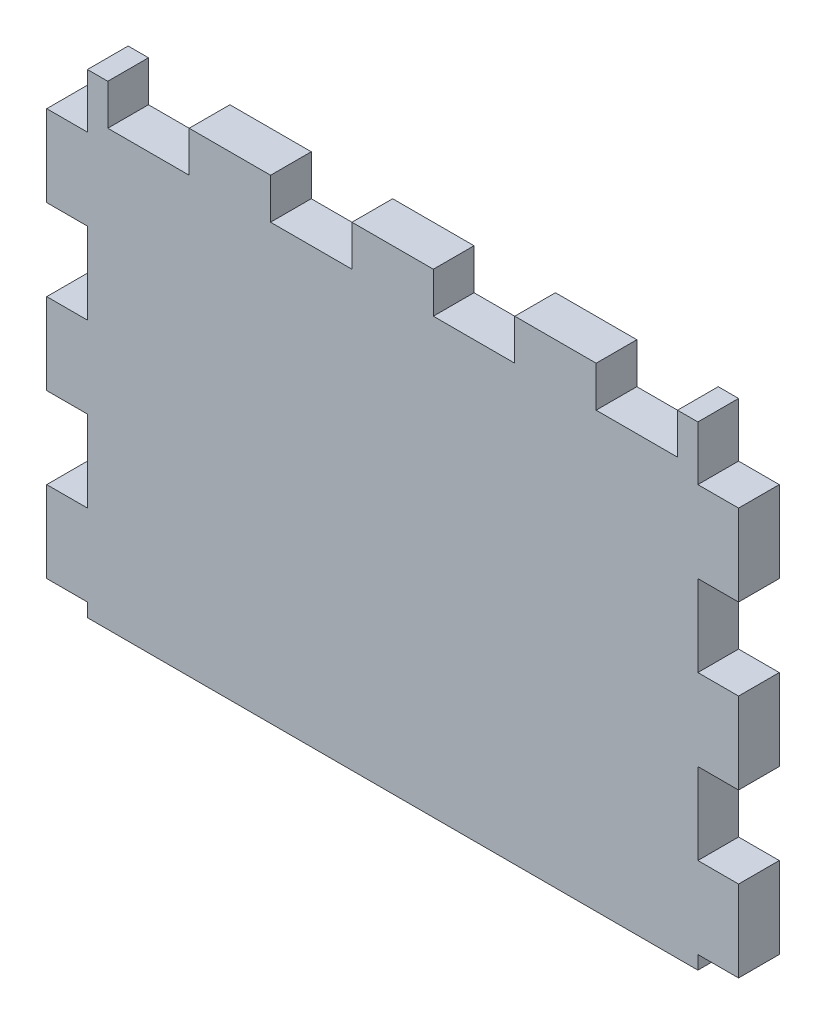
SolidWorks part; units mm, degrees
ref_plane "Front Plane" through (0, 0, 0) normal (0, 0, 1) x (1, 0, 0)
ref_plane "Top Plane" through (0, 0, 0) normal (0, 1, 0) x (1, 0, 0)
ref_plane "Right Plane" through (0, 0, 0) normal (1, 0, 0) x (0, 0, -1)
sketch "Sketch1" plane through (0, 0, 0) normal (0, 0, 1) x (1, 0, 0)
  line L1 (-22.5, 16) -> (22.5, 16)
  line L2 (-22.5, 16) -> (-22.5, -16)
  line L3 (-22.5, -16) -> (22.5, -16)
  line L4 (22.5, 16) -> (22.5, -16)
  line L5 (-22.5, 16) -> (22.5, -16) construction
  line L6 (-22.5, -16) -> (22.5, 16) construction
  point P0 (0, 0)
  dimension "D1" = 32
  dimension "D2" = 45
extrude "Boss-Extrude1" add sketch "Sketch1" along normal blind 3
sketch "Sketch2" plane through (-22.5, 0, 0) normal (-1, 0, 0) x (0, 0, 1)
  line L0 (0, 0) -> (3, 0) construction
  line L1 (0, 16) -> (0, -16) construction
  line L2 (3, 16) -> (3, -16) construction
  line L4 (3, 3) -> (0, 3)
  line L5 (3, 3) -> (3, -3)
  line L6 (3, -3) -> (0, -3)
  line L7 (0, 3) -> (0, -3)
  line L8 (3, 3) -> (0, -3) construction
  line L9 (3, -3) -> (0, 3) construction
  point P6 (1.5, 0)
  dimension "D1" = 6
extrude "Boss-Extrude2" add sketch "Sketch2" along normal blind 3
pattern_linear "LPattern1" count 2 spacing 12 along (0, -1, 0) count 2 spacing 12 along (0, 1, 0) of "Boss-Extrude2" pattern seed only yes
sketch "Sketch3" plane through (0, 16, 0) normal (0, 1, 0) x (1, 0, 0)
  line L0 (0, 0) -> (0, -3) construction
  line L1 (22.5, 0) -> (-22.5, 0) construction
  line L2 (22.5, -3) -> (-22.5, -3) construction
  line L4 (-3, 0) -> (3, 0)
  line L5 (-3, 0) -> (-3, -3)
  line L6 (-3, -3) -> (3, -3)
  line L7 (3, 0) -> (3, -3)
  line L8 (-3, 0) -> (3, -3) construction
  line L9 (-3, -3) -> (3, 0) construction
  point P6 (0, -1.5)
  dimension "D1" = 6
extrude "Boss-Extrude3" add sketch "Sketch3" along normal blind 3
pattern_linear "LPattern2" count 3 spacing 12 along (-1, 0, 0) count 3 spacing 12 along (1, 0, 0) of "Boss-Extrude3" pattern seed only yes
ref_plane "Plane1" through (0, 0, 0) normal (1, 0, 0) x (0, 0, -1)
sketch "Sketch5" plane through (0, 0, 0) normal (0, 0, -1) x (-1, 0, 0)
  line L0 (21, 19) -> (27, 19) construction
  line L1 (27, 16) -> (22.5, 16)
  line L2 (27, 16) -> (27, 19)
  line L3 (27, 19) -> (22.5, 19)
  line L4 (22.5, 16) -> (22.5, 19)
  line L5 (27, 16) -> (22.5, 19) construction
  line L6 (27, 19) -> (22.5, 16) construction
  line L8 (22.5, 16) -> (22.5, 15) construction
  point P4 (24.75, 17.5)
extrude "Cut-Extrude1" cut sketch "Sketch5" against normal blind 3
mirror "Mirror1" about plane through (0, 0, 0) normal (1, 0, 0) of "LPattern1"
mirror "Mirror2" about plane through (0, 0, 0) normal (1, 0, 0) of "Cut-Extrude1"
